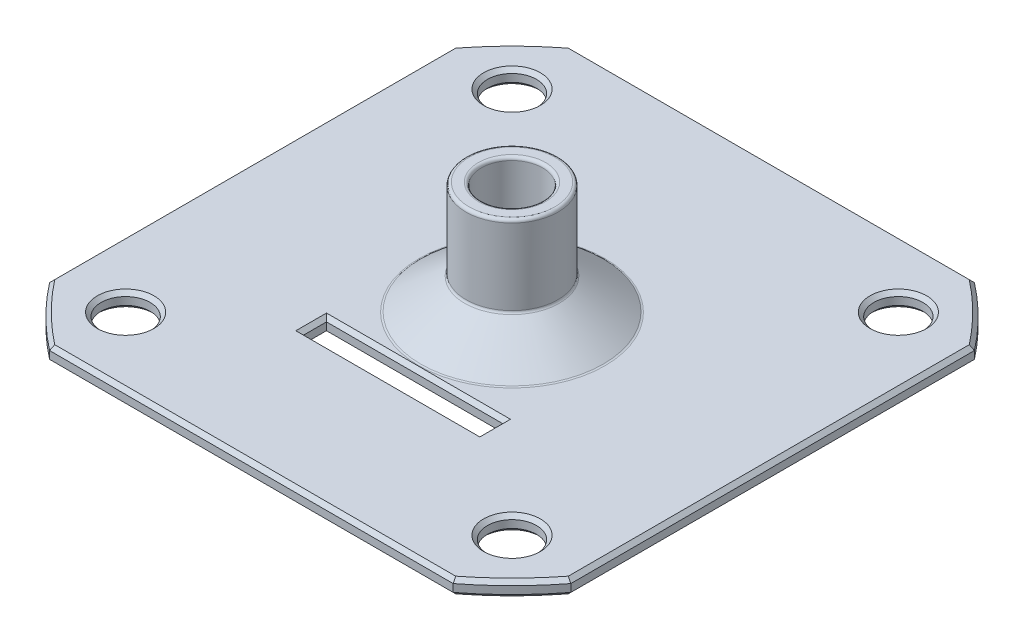
SolidWorks part; units mm, degrees
ref_plane "Front Plane" through (0, 0, 0) normal (0, 0, 1) x (1, 0, 0)
ref_plane "Top Plane" through (0, 0, 0) normal (0, 1, 0) x (1, 0, 0)
ref_plane "Right Plane" through (0, 0, 0) normal (1, 0, 0) x (0, 0, -1)
ref_axis "X Axis" through (-88.99, 0, 0) along (1, 0, 0)
ref_axis "Y Axis" through (0, 55, 0) along (0, -1, 0)
ref_axis "Z Axis" through (0, 0, -88.99) along (0, 0, 1)
sketch "Sketch1" plane through (0, 0, 0) normal (1, 0, 0) x (0, 0, -1)
  line L0 (0, 0) -> (0, 8.35) construction
  line L1 (3, 8.35) -> (2, 8.35)
  line L8 (2, 8.35) -> (2, 5.2)
  line L15 (0, 1.2) -> (2.125, 1.2) construction
  line L16 (2.125, 1.2) -> (2.125, 0) construction
  line L21 (2.125, 0) -> (0, 0) construction
  line L22 (2, 5.2) -> (0, 5.2)
  line L23 (0, 5.2) -> (0, 4.5909)
  line L32 (3, 8.35) -> (3, 3.1006)
  line L33 (0, 4.5909) -> (5.1283, 1)
  line L34 (6, 1) -> (6, 0)
  line L35 (6, 0) -> (5.1283, 0)
  line L36 (5.1283, 1) -> (5.1283, 0)
  line L37 (3, 3.1006) -> (6, 1)
  dimension "D1" = 55
  dimension "D2" = 0.5
  dimension "D3" = 4
  dimension "D4" = 3.15
  dimension "D5" = 2.125
  dimension "D6" = 1.2
  dimension "D7" = 4
  dimension "D8" = 12
  dimension "D9" = 1
  dimension "D10" = 1
revolve "Revolve1" add sketch "Sketch1" angle 360 about L0
sketch "Sketch2" plane through (0, 0, 0) normal (0, 1, 0) x (1, 0, 0)
  line L0 (17, 13.1624) -> (17, -13.1624)
  line L1 (-5.75, -6.35) -> (5.75, -6.35)
  line L2 (-5.75, -6.35) -> (-5.75, -7.85)
  line L3 (-5.75, -7.85) -> (5.75, -7.85)
  line L4 (5.75, -6.35) -> (5.75, -7.85)
  line L5 (13.1624, -17) -> (-13.1624, -17)
  line L6 (-17, -13.1624) -> (-17, 13.1624)
  line L7 (-13.1624, 17) -> (13.1624, 17)
  circle A0 centre (0, 0) radius 6 construction
  circle A1 centre (0, 0) radius 6
  circle A2 centre (0, 0) radius 17.82 construction
  circle A3 centre (0, 0) radius 21.5
  circle A4 centre (12.6006, 12.6006) radius 1.6
  circle A5 centre (12.6006, -12.6006) radius 1.6
  circle A6 centre (-12.6006, -12.6006) radius 1.6
  circle A7 centre (-12.6006, 12.6006) radius 1.6
  point P0 (0, 0)
  point P9 (14.7992, 20.3208)
  point P17 (0, -7.85)
  point P21 (0, 0)
  point P23 (0, -0.4173)
  point P24 (0, 0)
  point P31 (0, 0)
  dimension "D1" = 35.64
  dimension "D2" = 43
  dimension "D3" = 3.2
  dimension "D4" = 6.35
  dimension "D5" = 11.5
  dimension "D6" = 1.5
  dimension "D8" = 17
  dimension "D7" = 4
  dimension "D9" = 4
extrude "Boss-Extrude1" add sketch "Sketch2" along normal blind 1 contours L5 A3 L0 L7 L6 A7 A6 A5 A4 L1 L4 L3 L2 A1 region at (16.5192, 0, 0)
fillet "Fillet1" radius 0.2 6 edges at (0, 8.35, -2) (0, 8.35, -3) (0, 5.2, -2) (0, 1, -5.1283) (0, 3.1006, -3) (0, 1, -6)
chamfer "Chamfer1" distance 0.25 angle 45 33 edges at (0, 0, -5.1283) (15.2028, 0, 15.2028) (17, 0, 0) (15.2028, 0, -15.2028) (0, 0, -17) (-15.2028, 0, -15.2028) (-17, 0, 0) (-15.2028, 0, 15.2028) (0, 0, 17) (5.75, 0, 7.1) (0, 0, 7.85) (-5.75, 0, 7.1) (0, 0, 6.35) (12.6006, 0, -11.0006) (12.6006, 0, 14.2006) (-12.6006, 0, 14.2006) (-12.6006, 0, -11.0006) (-15.2028, 1, 15.2028) (-17, 1, 0) (-15.2028, 1, -15.2028) (0, 1, -17) (15.2028, 1, -15.2028) (17, 1, 0) (15.2028, 1, 15.2028) (0, 1, 17) (-5.75, 1, 7.1) (0, 1, 7.85) (5.75, 1, 7.1) (0, 1, 6.35) (12.6006, 1, -11.0006) (12.6006, 1, 14.2006) (-12.6006, 1, 14.2006) (-12.6006, 1, -11.0006)
